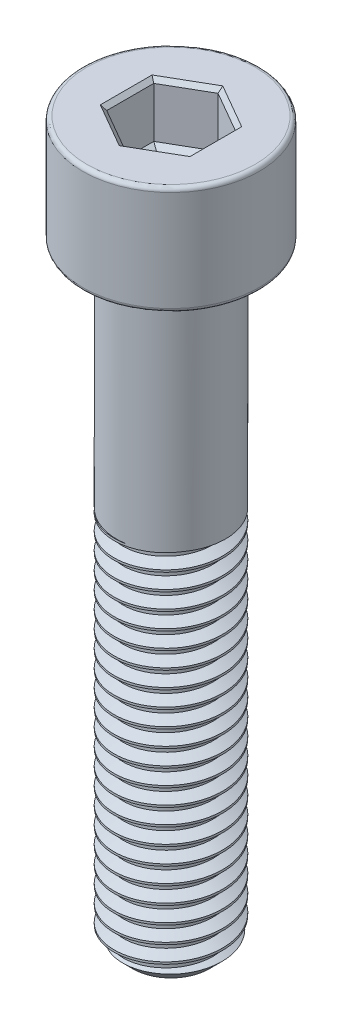
SolidWorks part; units mm, degrees
material "AISI Type A2 Tool Steel"
ref_plane "Front Plane" through (0, 0, 0) normal (0, 0, 1) x (1, 0, 0)
ref_plane "Top Plane" through (0, 0, 0) normal (0, 1, 0) x (1, 0, 0)
ref_plane "Right Plane" through (0, 0, 0) normal (1, 0, 0) x (0, 0, -1)
sketch "Sketch1" plane through (0, 0, 0) normal (0, 1, 0) x (1, 0, 0)
  circle A0 centre (0, 0) radius 4
  dimension "D1" = 8
extrude "Boss-Extrude1" add sketch "Sketch1" along normal blind 28
thread "Thread1" pitch 1.25 method cut profile "Thread Profile1" start angle 0, offset 2, length 0, pitch 1.25, diameter 8
ref_plane "Plane1" through (-4, 30, 0) normal (0, 0, 1) x (-1, 0, 0)
sketch "Thread Profile1" plane through (-4, 30, 0) normal (0, 0, 1) x (-1, 0, 0)
  line L0 (0, 0) -> (0, 1.25) construction
  line L11 (0, 0) -> (0, 1.0937)
  line L12 (0, 1.0937) -> (-0.6766, 0.7031)
  line L13 (-0.6766, 0.7031) -> (-0.6766, 0.3906)
  line L15 (-0.6766, 0.3906) -> (0, 0)
  line L17 (-0.6766, 0.5469) -> (0, 0.5469) construction
  point P2 (0, 0)
  dimension "Pitch" = 1.25
  dimension "Profile_Angle" = 60
  dimension "Profile_Land" = 0.3125
  dimension "Profile_Height" = 0.6766
sketch "Sketch2" plane through (0, 28, 0) normal (0, 1, 0) x (1, 0, 0)
  circle A0 centre (0, 0) radius 4
  dimension "D1" = 8
extrude "Boss-Extrude2" add sketch "Sketch2" along normal blind 17
sketch "Sketch5" plane through (0, 45, 0) normal (0, 1, 0) x (1, 0, 0)
  circle A0 centre (0, 0) radius 6.5
  dimension "D1" = 13
extrude "Boss-Extrude3" add sketch "Sketch5" along normal blind 8
sketch "Sketch6" plane through (0, 0, 0) normal (0, 0, 1) x (1, 0, 0)
  line L0 (0, 0) -> (0, 0.7245) construction
  line L1 (0, 0) -> (4.01, 0) construction
  line L2 (4.01, 0) -> (4.01, 1.2)
  line L3 (4.01, 1.2) -> (2.81, 0)
  line L4 (2.81, 0) -> (4.01, 0)
  dimension "D1" = 1.2
  dimension "D2" = 45
  dimension "D3" = 4.01
revolve "Cut-Revolve1" cut sketch "Sketch6" angle 360 about L0
fillet "Fillet1" radius 0.3 2 edges at (0, 45, 6.5) (0, 53, 6.5)
sketch "Sketch7" plane through (0, 53, 0) normal (0, 1, 0) x (1, 0, 0)
  line L1 (0, 3.4641) -> (-3, 1.7321)
  line L2 (-3, 1.7321) -> (-3, -1.7321)
  line L3 (-3, -1.7321) -> (0, -3.4641)
  line L4 (0, -3.4641) -> (3, -1.7321)
  line L5 (3, -1.7321) -> (3, 1.7321)
  line L6 (3, 1.7321) -> (0, 3.4641)
  circle A0 centre (0, 0) radius 3 construction
  dimension "D1" = 6
extrude "Cut-Extrude1" cut sketch "Sketch7" against normal blind 4
chamfer "Chamfer1" distance 0.3 angle 45 6 edges at (-3, 53, 0) (-1.5, 53, 2.5981) (1.5, 53, 2.5981) (3, 53, 0) (1.5, 53, -2.5981) (-1.5, 53, -2.5981)
sketch "Sketch8" plane through (0, 49, 0) normal (0, 1, 0) x (1, 0, 0)
  line L1 (0, 3.4641) -> (-3, 1.7321)
  line L2 (-3, 1.7321) -> (-3, -1.7321)
  line L3 (-3, -1.7321) -> (0, -3.4641)
  line L4 (0, -3.4641) -> (3, -1.7321)
  line L5 (3, -1.7321) -> (3, 1.7321)
  line L6 (3, 1.7321) -> (0, 3.4641)
  circle A0 centre (0, 0) radius 3 construction
extrude "Cut-Extrude2" cut sketch "Sketch8" against normal blind 0.4 draft 60
